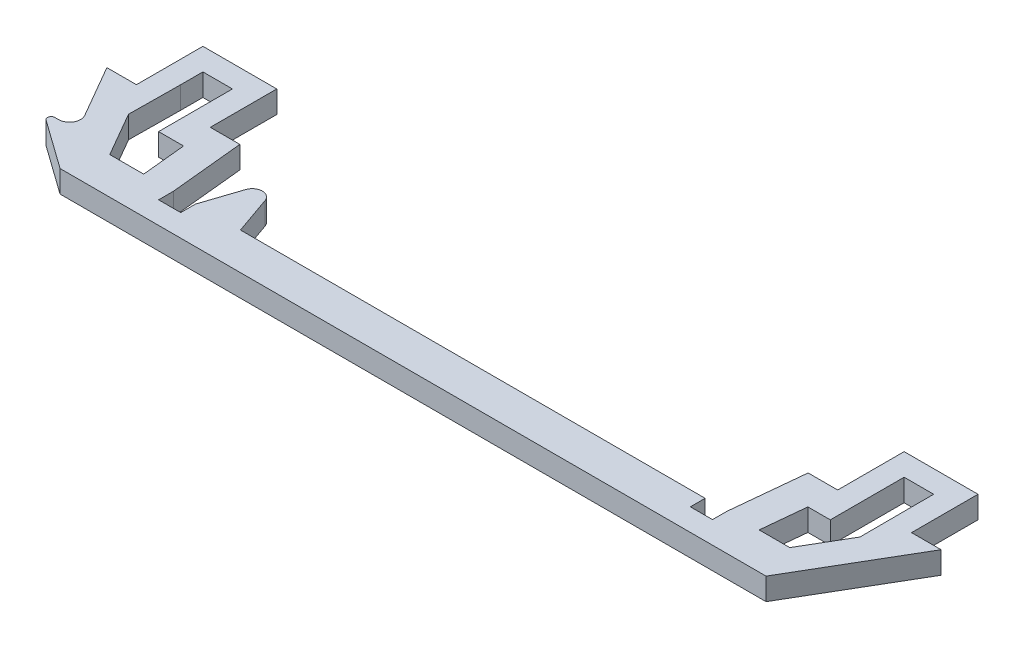
SolidWorks part; units mm, degrees
material "Custom Plastic"
ref_plane "Front Plane" through (0, 0, 0) normal (0, 0, 1) x (1, 0, 0)
ref_plane "Top Plane" through (0, 0, 0) normal (0, 1, 0) x (1, 0, 0)
ref_plane "Right Plane" through (0, 0, 0) normal (1, 0, 0) x (0, 0, -1)
sketch "Sketch1" plane through (0, 0, 0) normal (0, 1, 0) x (1, 0, 0)
  line L0 (-62.4186, -47.1587) -> (-58.4186, -47.1587)
  line L1 (-58.4186, -47.1587) -> (-58.4186, -38.1587)
  line L2 (-58.4186, -38.1587) -> (-48.4186, -38.1587)
  line L3 (-48.4186, -38.1587) -> (-48.4186, -47.1587)
  line L4 (-48.4186, -47.1587) -> (-44.4186, -47.1587)
  line L5 (-44.4186, -47.1587) -> (-43.4188, -57.1562)
  line L7 (31.5814, -57.2088) -> (32.5814, -47.2113)
  line L8 (32.5814, -47.2113) -> (36.5814, -47.2113)
  line L9 (36.5814, -47.2113) -> (36.5814, -38.2113)
  line L10 (36.5814, -38.2113) -> (46.5814, -38.2113)
  line L11 (46.5814, -38.2113) -> (46.5814, -47.2113)
  line L12 (46.5814, -47.2113) -> (50.5814, -47.2113)
  line L13 (50.5814, -47.2113) -> (41.8306, -62.1587)
  line L14 (41.8306, -62.1587) -> (-53.7583, -62.1587)
  line L15 (-58.3105, -54.274) -> (-62.4186, -47.1587)
  line L16 (36.5478, -51.2113) -> (39.5814, -51.2113)
  line L17 (-55.4186, -41.1587) -> (-51.4186, -41.1587)
  line L18 (-55.4186, -41.1587) -> (-55.4186, -44.1587)
  line L20 (-51.4186, -41.1587) -> (-51.4186, -44.1587)
  line L21 (39.5814, -41.2113) -> (43.5814, -41.2113)
  line L22 (39.5814, -41.2113) -> (39.5814, -44.2113)
  line L24 (43.5814, -41.2113) -> (43.5814, -44.2113)
  line L25 (43.6046, -51.2113) -> (40.0934, -57.2088)
  line L26 (40.0934, -57.2088) -> (35.9479, -57.2088)
  line L27 (35.9479, -57.2088) -> (36.5478, -51.2113)
  line L28 (-51.4186, -51.1587) -> (-48.0385, -51.1587)
  line L29 (-48.0385, -51.1587) -> (-47.4385, -57.1587)
  line L30 (-47.4385, -57.1587) -> (-52.0263, -57.1587)
  line L31 (-52.0263, -57.1587) -> (-55.4904, -51.1587)
  line L32 (28.5814, -57.1587) -> (28.5814, -59.1587)
  line L33 (28.5814, -47.1587) -> (28.5814, -62.1587) construction
  line L34 (28.5814, -59.1587) -> (31.5814, -59.1587)
  line L35 (31.5814, -59.1587) -> (31.5814, -57.2088)
  line L36 (31.5814, -62.1587) -> (31.5814, -47.1587) construction
  line L38 (-43.4188, -57.1562) -> (-43.4188, -59.1587)
  line L39 (-43.4188, -59.1587) -> (-40.4188, -59.1587)
  line L40 (-40.4188, -59.1587) -> (-40.4188, -57.1587)
  line L41 (-34.3352, -57.1587) -> (28.5814, -57.1587)
  line L42 (-34.3352, -57.1587) -> (-36.1291, -52.0241)
  line L43 (43.5814, -44.2113) -> (43.6046, -51.2113)
  line L44 (-38.7227, -52.0447) -> (-40.4188, -57.1587)
  line L45 (39.5814, -44.2113) -> (39.5814, -51.2113)
  line L46 (-55.4186, -44.1587) -> (-55.4904, -51.1587)
  line L47 (-51.4186, -44.1587) -> (-51.4186, -51.1587)
  line L48 (-53.7583, -62.1587) -> (-60.3821, -57.431)
  line L49 (-60.0916, -56.524) -> (-59.6096, -56.524)
  arc A0 (-38.7227, -52.0447) -> (-36.1291, -52.0241) centre (-37.4224, -52.4759) cw
  arc A1 (-59.6096, -56.524) -> (-58.3105, -54.274) centre (-59.6096, -55.024) ccw
  arc A2 (-60.3821, -57.431) -> (-60.0916, -56.524) centre (-60.0916, -57.024) cw
  point P56 (0, 0)
  point P57 (0, 0)
  point P58 (28.5814, -59.7154)
  dimension "D6" = 0.5
  dimension "D5" = 1.5
  dimension "D1" = 15
  dimension "D2" = 4
  dimension "D3" = 9
  dimension "D4" = 3
  dimension "D7" = 120
  dimension "D8" = 10
  dimension "D9" = 85
  dimension "D10" = 3
  dimension "D12" = 3
  dimension "D13" = 3
  dimension "D14" = 3
  dimension "D15" = 3
  dimension "D17" = 4
  dimension "D18" = 4
  dimension "D19" = 4
  dimension "D20" = 4
  dimension "D21" = 4
  dimension "D23" = 2
  dimension "D24" = 3
extrude "Boss-Extrude1" add sketch "Sketch1" along normal blind 3
